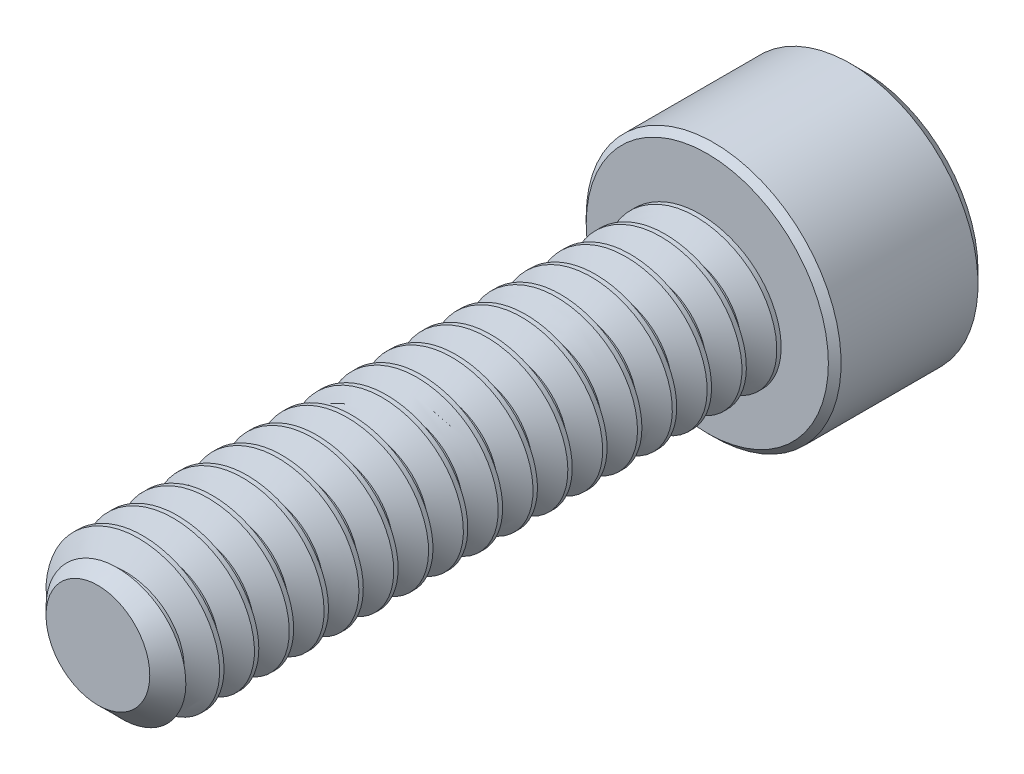
SolidWorks part; units mm, degrees
ref_plane "Front Plane" through (0, 0, 0) normal (0, 0, 1) x (1, 0, 0)
ref_plane "Top Plane" through (0, 0, 0) normal (0, 1, 0) x (1, 0, 0)
ref_plane "Right Plane" through (0, 0, 0) normal (1, 0, 0) x (0, 0, -1)
sketch "Sketch0" plane through (0, 0, 0) normal (1, 0, 0) x (0, 0, -1)
  line L0 (0, 0) -> (11.1125, 0) construction
  point P2 (13.9573, 0)
  point P4 (0, 0)
  dimension "D1" = 11.1125
  dimension "D2" = 2.8448
  dimension "Min Thread" = 0
sketch "Sketch1" plane through (0, 0, 0) normal (0, 0, 1) x (1, 0, 0)
  circle A0 centre (0, 0) radius 1.4224
  dimension "OD" = 2.8448
extrude "Extrude1" add sketch "Sketch1" against normal blind 11.1125
sketch "Sketch2" plane through (0, 0, 0) normal (0, 0, 1) x (1, 0, 0)
  circle A0 centre (0, 0) radius 1.4224 construction
  circle A1 centre (0, 0) radius 1.4224
curve "Helix/Spiral1" pitch 0.635 height 11.7475 turns 18.5 parameters "pitch"=0.635
chamfer "Chamfer3" distance 0.4763 angle 45 1 edges at (1.4224, 0, 0)
sketch "Sketch3" plane through (0, 0, 0) normal (1, 0, 0) x (0, 0, -1)
  line L0 (-0.5556, 1.4224) -> (-0.3175, 1.01)
  line L1 (-0.3175, 1.01) -> (-0.2381, 1.01)
  line L2 (-0.2381, 1.01) -> (0, 1.4224)
  line L3 (-0.5556, 1.4224) -> (0, 1.4224)
  line L4 (-0.2778, 1.4224) -> (-0.2778, 1.01) construction
  line L5 (-0.4366, 1.2162) -> (-0.1191, 1.2162) construction
  line L6 (0, 1.4224) -> (0, -1.4224) construction
  dimension "D1" = 0.0794
  dimension "D2" = 0.3175
  dimension "D3" = 60
sweep "Cut-Sweep1" cut profiles "Sketch3" path "Helix/Spiral1" align with end faces yes
sketch "Sketch5" plane through (0, 0, 0) normal (1, 0, 0) x (0, 0, -1)
  line L0 (11.1125, -1.0149) -> (11.1125, 1.0232) construction
  line L1 (11.1125, 1.4224) -> (0, 1.4224)
  line L2 (11.1125, 1.4224) -> (11.1125, 0)
  line L3 (11.1125, 0) -> (-0.5177, 0)
  line L4 (0, 0) -> (11.1125, 0) construction
  line L5 (0, 1.4224) -> (-0.5177, 0)
  line L6 (0, 0) -> (13.6525, 0) construction
  dimension "D1" = 70
  dimension "D3" = 2.54
revolve "partially thread" [suppressed] add sketch "Sketch5" angle 360 about L6
sketch "Sketch6" plane through (0, 0, -11.1125) normal (0, 0, -1) x (-1, 0, 0)
  circle A0 centre (0, 0) radius 2.3241
  dimension "head dia" = 4.6482
extrude "Extrude2" add sketch "Sketch6" along normal blind 2.8448
sketch "Sketch7" plane through (0, 0, -13.9573) normal (0, 0, -1) x (-1, 0, 0)
  line L1 (0, 1.3748) -> (-1.1906, 0.6874)
  line L2 (-1.1906, 0.6874) -> (-1.1906, -0.6874)
  line L3 (-1.1906, -0.6874) -> (0, -1.3748)
  line L4 (0, -1.3748) -> (1.1906, -0.6874)
  line L5 (1.1906, -0.6874) -> (1.1906, 0.6874)
  line L6 (1.1906, 0.6874) -> (0, 1.3748)
  circle A0 centre (0, 0) radius 1.1906 construction
  dimension "hex dia" = 2.3813
extrude "Cut-Extrude1" cut sketch "Sketch7" against normal blind 1.7859
sketch "Sketch8" plane through (0, 0, -13.9573) normal (0, 0, -1) x (-1, 0, 0)
  circle A0 centre (0, 0) radius 1.3748
extrude "Cut-Extrude2" cut sketch "Sketch8" against normal through all draft 45
chamfer "Chamfer1" distance 0.2324 angle 45 1 edges at (-2.3241, 0, -13.9573)
chamfer "Chamfer2" distance 0.1162 angle 45 1 edges at (-2.3241, 0, -11.1125)
sketch "Sketch9" plane through (0, 0, 0) normal (1, 0, 0) x (0, 0, -1)
  line L0 (0, 1.4224) -> (0, -1.4224) construction
  line L1 (1.5875, 1.4224) -> (1.5875, -1.4224) construction
  line L2 (13.9573, 2.3241) -> (13.9573, -2.3241) construction
  line L3 (11.1125, 2.3241) -> (11.1125, -2.3241) construction
  line L4 (11.1125, 2.2079) -> (11.1125, -2.2079) construction
  line L5 (13.9573, -2.0917) -> (13.9573, 2.0917) construction
  line L6 (11.1125, -2.3241) -> (11.1125, 2.3241) construction
  line L7 (0, 0.9462) -> (0, -0.9462) construction
  line L8 (-0.5556, 1.4224) -> (0, 1.4224) construction
  line L9 (1.5875, 0) -> (0, 0) construction
  dimension "D1" = 1.5875
equation "\"D3@Helix/Spiral1\" = \"screw length@Extrude1\"+\"pitch@Helix/Spiral1\""
equation "\"D1@Sketch3\" = \"pitch@Helix/Spiral1\"*.125"
equation "\"D2@Sketch3\" = \"pitch@Helix/Spiral1\"*.5"
equation "\"D1@Cut-Extrude1\" = \"hex dia@Sketch7\"*.75"
equation "\"D1@Chamfer1\" = \"head dia@Sketch6\"*.05"
equation "\"D1@Sketch9\" = \"pitch@Helix/Spiral1\"*2.50"
equation "\"D1@Chamfer2\" = \"D1@Chamfer1\"/2"
equation "\"D1@Chamfer3\" = \"pitch@Helix/Spiral1\"*.750"
equation "\"D1@Sketch0\" = \"screw length@Extrude1\""
equation "\"D2@Sketch0\" = \"head depth@Extrude2\""
